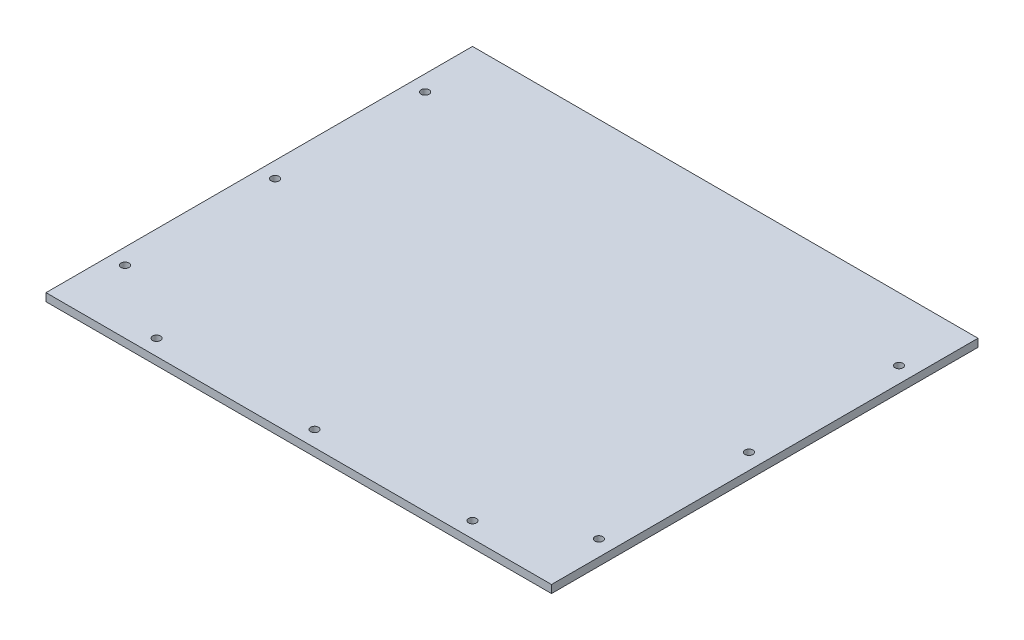
SolidWorks part; units mm, degrees
ref_plane "Front Plane" through (0, 0, 0) normal (0, 0, 1) x (1, 0, 0)
ref_plane "Top Plane" through (0, 0, 0) normal (0, 1, 0) x (1, 0, 0)
ref_plane "Right Plane" through (0, 0, 0) normal (1, 0, 0) x (0, 0, -1)
sketch "Sketch1" plane through (0, 0, 0) normal (0, 1, 0) x (1, 0, 0)
  line L0 (406.4, 0) -> (406.4, 342.9) construction
  line L1 (0, 0) -> (406.4, 0)
  line L2 (0, 0) -> (0, 342.9)
  line L3 (0, 342.9) -> (406.4, 342.9)
  line L4 (406.4, 0) -> (406.4, 342.9)
  line L5 (406.4, 0) -> (406.4, 342.9) construction
  line L6 (387.3669, 342.9) -> (384.1496, 342.9) construction
  line L7 (387.3669, 342.9) -> (384.1496, 342.9) construction
extrude "Boss-Extrude1" add sketch "Sketch1" along normal blind 6.35
sketch "Sketch3" plane through (0, 6.35, 0) normal (0, 1, 0) x (1, 0, 0)
  line L0 (0, 342.9) -> (0, 0) construction
  line L1 (25.4, 25.4) -> (381, 25.4) construction
  line L2 (25.4, 25.4) -> (25.4, 317.5) construction
  line L3 (25.4, 317.5) -> (381, 317.5) construction
  line L4 (381, 25.4) -> (381, 317.5) construction
  line L5 (0, 0) -> (406.4, 0) construction
  line L6 (406.4, 0) -> (406.4, 342.9) construction
  line L7 (406.4, 342.9) -> (0, 342.9) construction
  line L8 (0, 171.45) -> (406.4, 171.45) construction
  line L9 (203.2, 0) -> (203.2, 342.9) construction
  line L10 (12.7, 342.9) -> (12.7, 0) construction
  line L11 (393.7, 342.9) -> (393.7, 0) construction
  line L12 (406.4, 12.7) -> (0, 12.7) construction
  line L13 (12.7, 292.1) -> (393.7, 292.1) construction
  line L14 (12.7, 50.8) -> (393.7, 50.8) construction
  circle A0 centre (203.2, 12.7) radius 3.175
  circle A1 centre (330.2, 12.7) radius 3.175
  circle A2 centre (76.2, 12.7) radius 3.175
  circle A3 centre (12.7, 171.45) radius 3.175
  circle A4 centre (393.7, 171.45) radius 3.175
  circle A5 centre (12.7, 292.1) radius 3.175
  circle A6 centre (12.7, 50.8) radius 3.175
  circle A7 centre (393.7, 50.8) radius 3.175
  circle A8 centre (393.7, 292.1) radius 3.175
  dimension "D8" = 6.35
  dimension "D1" = 25.4
  dimension "D2" = 25.4
  dimension "D3" = 25.4
  dimension "D4" = 25.4
  dimension "D5" = 12.7
  dimension "D6" = 12.7
  dimension "D7" = 12.7
  dimension "D9" = 76.2
  dimension "D10" = 76.2
  dimension "D11" = 50.8
  dimension "D12" = 50.8
extrude "Cut-Extrude1" cut sketch "Sketch3" against normal through all
sketch "Sketch4" plane through (0, 6.35, 0) normal (0, 1, 0) x (1, 0, 0)
  line L0 (406.4, 342.9) -> (0, 342.9) construction
  line L1 (406.4, 0) -> (406.4, 342.9) construction
  line L2 (202.4563, 342.9) -> (203.2, 0) construction
  line L3 (0, 0) -> (406.4, 0) construction
  line L4 (267.4, 279.9) -> (100.0472, 279.9) construction
  circle A0 centre (267.4, 279.9) radius 9.525
  circle A1 centre (100.0472, 279.9) radius 9.525
  dimension "D1" = 19.05
  dimension "D2" = 63
  dimension "D3" = 139
equation "\"D9@Sketch3\"=3in"
